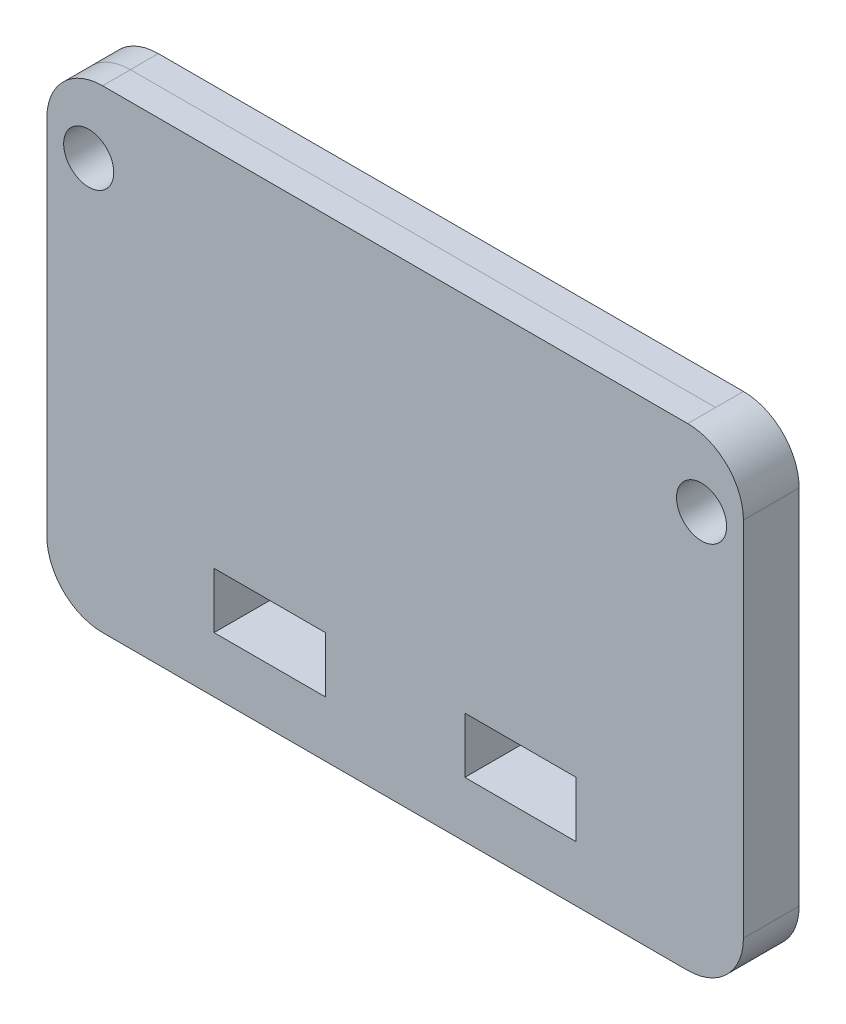
SolidWorks part; units mm, degrees
material "Pink Foam"
ref_plane "Front Plane" through (0, 0, 0) normal (0, 0, 1) x (1, 0, 0)
ref_plane "Top Plane" through (0, 0, 0) normal (0, 1, 0) x (1, 0, 0)
ref_plane "Right Plane" through (0, 0, 0) normal (1, 0, 0) x (0, 0, -1)
sketch "Sketch1" plane through (0, 0, 0) normal (0, 0, 1) x (1, 0, 0)
  line L1 (-139.7, -203.2) -> (139.7, -203.2) construction
  line L2 (-165.1, -177.8) -> (-165.1, 177.8) construction
  line L3 (-139.7, 203.2) -> (139.7, 203.2) construction
  line L4 (165.1, -177.8) -> (165.1, 177.8) construction
  line L5 (-165.1, -203.2) -> (165.1, 203.2) construction
  line L6 (-165.1, 203.2) -> (165.1, -203.2) construction
  line L7 (-133.3733, -107.95) -> (133.3733, -107.95)
  line L8 (-158.7733, -82.55) -> (-158.7733, 82.55)
  line L9 (-133.3733, 107.95) -> (133.3733, 107.95)
  line L10 (158.7733, -82.55) -> (158.7733, 82.55)
  line L11 (-158.7733, -107.95) -> (158.7733, 107.95) construction
  line L12 (-158.7733, 107.95) -> (158.7733, -107.95) construction
  arc A0 (-139.7, -203.2) -> (-165.1, -177.8) centre (-139.7, -177.8) cw construction
  arc A1 (139.7, -203.2) -> (165.1, -177.8) centre (139.7, -177.8) ccw construction
  arc A2 (139.7, 203.2) -> (165.1, 177.8) centre (139.7, 177.8) cw construction
  arc A3 (-165.1, 177.8) -> (-139.7, 203.2) centre (-139.7, 177.8) cw construction
  circle A4 centre (-139.7, 76.2) radius 11.422
  circle A5 centre (139.7, 76.2) radius 11.422
  arc A6 (-133.3733, -107.95) -> (-158.7733, -82.55) centre (-133.3733, -82.55) cw
  arc A7 (133.3733, -107.95) -> (158.7733, -82.55) centre (133.3733, -82.55) ccw
  arc A8 (133.3733, 107.95) -> (158.7733, 82.55) centre (133.3733, 82.55) cw
  arc A9 (-158.7733, 82.55) -> (-133.3733, 107.95) centre (-133.3733, 82.55) cw
  point P0 (0, 0)
  point P23 (0, 0)
  dimension "D3" = 25.4
  dimension "D7" = 22.844
  dimension "D8" = 317.5465
  dimension "D10" = 25.4
  dimension "D1" = 330.2
  dimension "D2" = 406.4
  dimension "D4" = 25.4
  dimension "D5" = 127
  dimension "D6" = 25.4
  dimension "D9" = 215.9
extrude "Boss-Extrude1" add sketch "Sketch1" along normal blind 25.4
ref_plane "Plane1" through (0, 0, 12.7) normal (0, 0, 1) x (1, 0, 0)
sketch "Sketch2" plane through (0, 0, 0) normal (0, 0, -1) x (-1, 0, 0)
  line L0 (0, 0) -> (0, -69.85) construction
  line L2 (-114.3, -69.85) -> (0, -69.85) construction
  line L3 (0, -69.85) -> (114.3, -69.85) construction
  line L4 (-82.55, -82.55) -> (-31.75, -82.55)
  line L5 (-82.55, -82.55) -> (-82.55, -57.15)
  line L6 (-82.55, -57.15) -> (-31.75, -57.15)
  line L7 (-31.75, -82.55) -> (-31.75, -57.15)
  line L8 (-82.55, -82.55) -> (-31.75, -57.15) construction
  line L9 (-82.55, -57.15) -> (-31.75, -82.55) construction
  line L10 (31.75, -82.55) -> (82.55, -82.55)
  line L11 (31.75, -82.55) -> (31.75, -57.15)
  line L12 (31.75, -57.15) -> (82.55, -57.15)
  line L13 (82.55, -82.55) -> (82.55, -57.15)
  line L14 (31.75, -82.55) -> (82.55, -57.15) construction
  line L15 (31.75, -57.15) -> (82.55, -82.55) construction
  point P5 (-57.15, -69.85)
  point P6 (57.15, -69.85)
  point P7 (-57.15, -69.85)
  point P12 (57.15, -69.85)
  dimension "D1" = 228.6
  dimension "D2" = 69.85
  dimension "D3" = 25.4
  dimension "D4" = 50.8
  dimension "D5" = 50.8
  dimension "D6" = 25.4
extrude "Foam Insert Cut-Throughs" cut sketch "Sketch2" against normal blind 25.4
split line "Split Line1"
